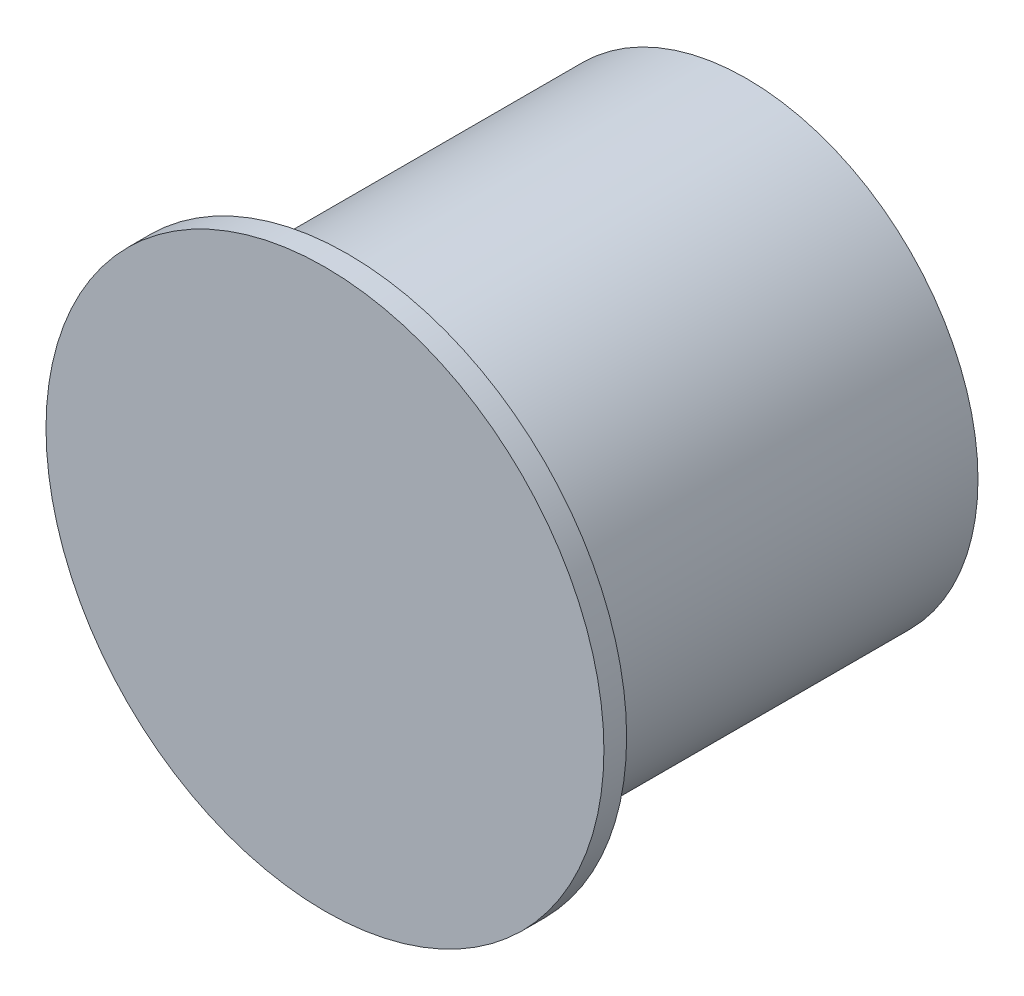
SolidWorks part; units mm, degrees
ref_plane "Front" through (0, 0, 0) normal (0, 0, 1) x (1, 0, 0)
ref_plane "Top" through (0, 0, 0) normal (0, 1, 0) x (1, 0, 0)
ref_plane "Right" through (0, 0, 0) normal (1, 0, 0) x (0, 0, -1)
sketch "Эскиз1" plane through (0, 0, 0) normal (0, 0, 1) x (1, 0, 0)
  circle A0 centre (0, 0) radius 196.5
extrude "Фланец" add sketch "Эскиз1" against normal blind 16
sketch "Эскиз3" plane through (0, 0, -16) normal (0, 0, -1) x (-1, 0, 0)
  circle A0 centre (0, 0) radius 163
  circle A1 centre (0, 0) radius 161
extrude "Внешняя стенка бочки" add sketch "Эскиз3" along normal blind 272 contours A0 | A1
ref_plane "Плоскость2" through (0, 0, -70) normal (0, 0, -1) x (-1, 0, 0)
sketch "Эскиз5" plane through (0, 0, -70) normal (0, 0, -1) x (-1, 0, 0)
  circle A0 centre (0, 0) radius 125
  circle A1 centre (0, 0) radius 119
extrude "Внутренняя стенка бочки" add sketch "Эскиз5" along normal blind 208 separate body
sketch "Эскиз6" plane through (0, 0, -278) normal (0, 0, -1) x (-1, 0, 0)
  circle A0 centre (0, 0) radius 125
extrude "Внутренняя стенка: дно" add sketch "Эскиз6" along normal blind 2
sketch "Эскиз7" plane through (0, 0, -288) normal (0, 0, -1) x (-1, 0, 0)
  circle A0 centre (0, 0) radius 163
extrude "Внешняя стенка: дно" add sketch "Эскиз7" along normal blind 9
sketch "Эскиз8" plane through (0, 0, -70) normal (0, 0, -1) x (-1, 0, 0)
  circle A0 centre (0, 0) radius 125
extrude "Внутренняя стенка: крышка" add sketch "Эскиз8" against normal blind 16 separate body
